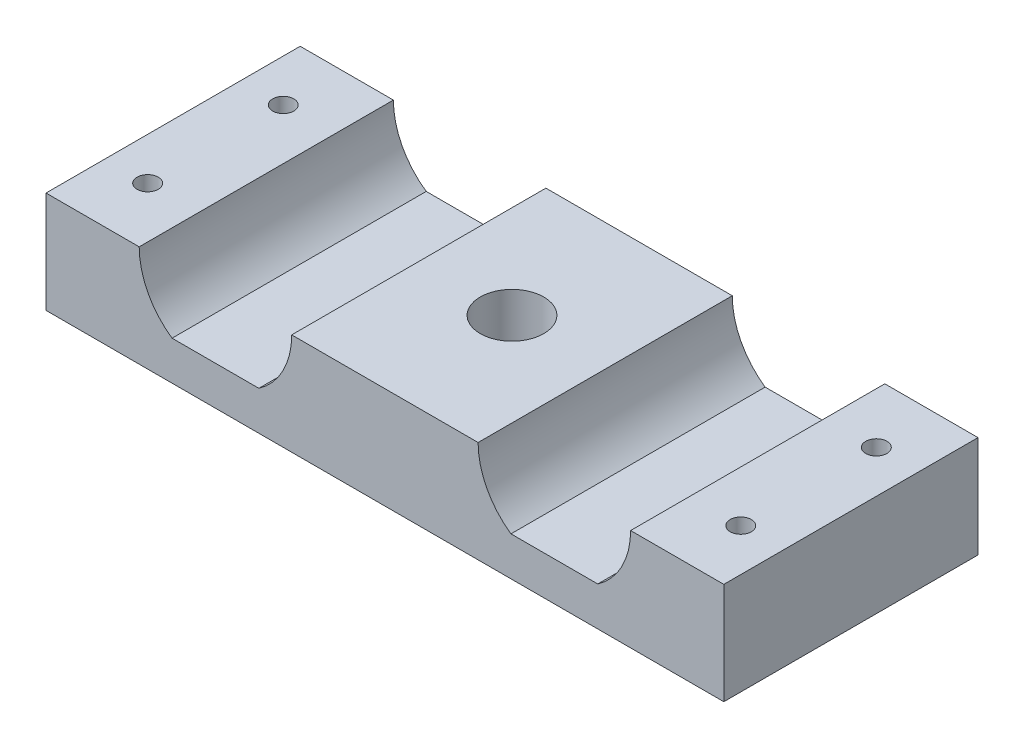
SolidWorks part; units mm, degrees
ref_plane "Front Plane" through (0, 0, 0) normal (0, 0, 1) x (1, 0, 0)
ref_plane "Top Plane" through (0, 0, 0) normal (0, 1, 0) x (1, 0, 0)
ref_plane "Right Plane" through (0, 0, 0) normal (1, 0, 0) x (0, 0, -1)
sketch "Sketch1" plane through (0, 0, 0) normal (0, 0, 1) x (1, 0, 0)
  line L0 (-50.8, 0) -> (50.8, 0)
  line L1 (50.8, 0) -> (50.8, 15.24)
  line L2 (50.8, 15.24) -> (36.83, 15.24)
  line L3 (25.4, 15.24) -> (51.7323, 15.24) construction
  line L4 (13.97, 15.24) -> (-13.97, 15.24)
  line L5 (31.9056, 5.842) -> (18.8944, 5.842)
  line L6 (0, 0) -> (0, 35.6145) construction
  line L7 (-25.4, 15.24) -> (-51.7323, 15.24) construction
  line L8 (-31.9056, 5.842) -> (-18.8944, 5.842)
  line L9 (-50.8, 15.24) -> (-36.83, 15.24)
  line L10 (-50.8, 0) -> (-50.8, 15.24)
  arc A0 (13.97, 15.24) -> (18.8944, 5.842) centre (25.4, 15.24) ccw
  arc A1 (31.9056, 5.842) -> (36.83, 15.24) centre (25.4, 15.24) ccw
  arc A2 (-31.9056, 5.842) -> (-36.83, 15.24) centre (-25.4, 15.24) cw
  arc A3 (-13.97, 15.24) -> (-18.8944, 5.842) centre (-25.4, 15.24) cw
  point P20 (0, 15.24)
  dimension "D1" = 22.86
  dimension "D2" = 9.398
  dimension "D3" = 15.24
  dimension "D4" = 25.4
  dimension "D5" = 50.8
extrude "Boss-Extrude1" add sketch "Sketch1" along normal blind 38.1
hole_wizard "Hole1" positions "Sketch2" profile "Sketch3" legacy
sketch "Sketch2" plane through (0, 15.24, 0) normal (0, 1, 0) x (1, 0, 0)
  point P0 (0, -19.05)
  dimension "D1" = 19.05
sketch "Sketch3" plane through (0, 15.24, 19.05) normal (1, 0, 0) x (0, 0, 1)
  line L0 (0, 0) -> (0, 101.6)
  line L1 (0, 101.6) -> (4.7625, 101.6)
  line L2 (4.7625, 101.6) -> (4.7625, 0)
  line L3 (4.7625, 0) -> (0, 0)
  line L4 (0, 110) -> (0, -10) construction
  dimension "Diameter" = 9.525
  dimension "Depth" = 101.6
hole_wizard "Hole2" positions "Sketch4" profile "Sketch5" legacy
sketch "Sketch4" plane through (0, 15.24, 0) normal (0, 1, 0) x (1, 0, 0)
  point P0 (-44.45, -8.89)
  dimension "D1" = 44.45
  dimension "D2" = 8.89
sketch "Sketch5" plane through (-44.45, 15.24, 8.89) normal (1, 0, 0) x (0, 0, 1)
  line L0 (0, 0) -> (0, 101.6)
  line L1 (0, 101.6) -> (1.5875, 101.6)
  line L2 (1.5875, 101.6) -> (1.5875, 0)
  line L3 (1.5875, 0) -> (0, 0)
  line L4 (0, 110) -> (0, -10) construction
  dimension "Diameter" = 3.175
  dimension "Depth" = 101.6
pattern_linear "LPattern1" count 2 spacing 20.32 along (0, 0, 1) count 2 spacing 88.9 along (1, 0, 0) of "Hole2"
